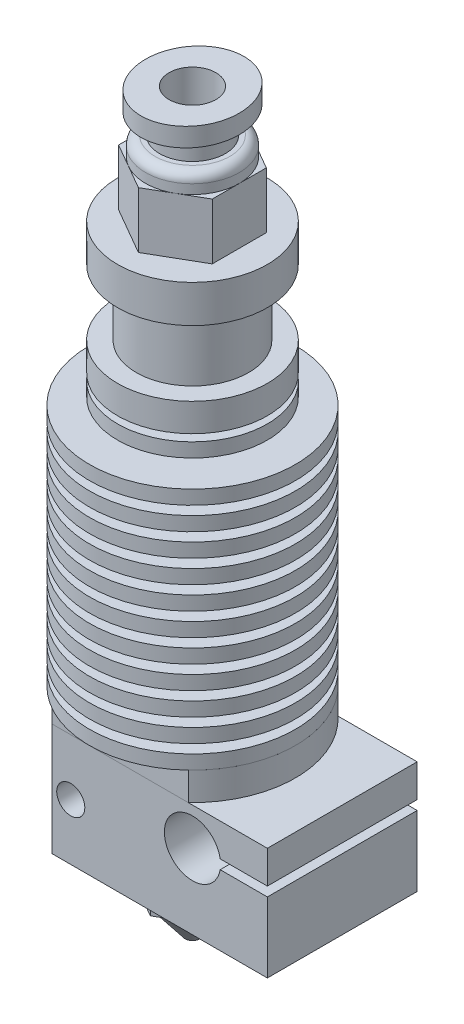
SolidWorks part; units mm, degrees
material "Bronce de aluminio"
ref_plane "Alzado" through (0, 0, 0) normal (0, 0, 1) x (1, 0, 0)
ref_plane "Planta" through (0, 0, 0) normal (0, 1, 0) x (1, 0, 0)
ref_plane "Vista lateral" through (0, 0, 0) normal (1, 0, 0) x (0, 0, -1)
sketch "Croquis1" plane through (0, 0, 0) normal (0, 0, 1) x (1, 0, 0)
  line L0 (0, 0) -> (-8, 0)
  line L1 (-8, 0) -> (-8, -4)
  line L2 (-8, -4) -> (-6, -4)
  line L3 (-6, -4) -> (-6, -11)
  line L4 (-6, -11) -> (-8, -11)
  line L5 (-8, -11) -> (-8, -14)
  line L6 (-8, -14) -> (-5, -14)
  line L7 (-5, -14) -> (-5, -14.75)
  line L8 (-5, -14.75) -> (-8, -14.75)
  line L9 (-8, -14.75) -> (-8, -16.25)
  line L10 (-8, -16.25) -> (-5, -16.25)
  line L12 (-5, -17) -> (-11, -17)
  line L13 (-11, -17) -> (-11, -18.5)
  line L17 (-5, -16.25) -> (-5, -17)
  line L18 (-11, -18.5) -> (-5, -18.5)
  line L19 (-5, -18.5) -> (-5, -19.45)
  line L20 (-5, -19.45) -> (-11, -19.45)
  line L21 (-11, -19.45) -> (-11, -20.95)
  line L22 (-11, -20.95) -> (-5, -20.95)
  line L23 (-5, -20.95) -> (-5, -21.9)
  line L24 (-5, -21.9) -> (-11, -21.9)
  line L25 (-11, -21.9) -> (-11, -23.4)
  line L26 (-11, -23.4) -> (-5, -23.4)
  line L27 (-5, -23.4) -> (-5, -24.35)
  line L28 (-5, -24.35) -> (-11, -24.35)
  line L29 (-11, -24.35) -> (-11, -25.85)
  line L30 (-11, -25.85) -> (-5, -25.85)
  line L31 (-5, -25.85) -> (-5, -26.8)
  line L32 (-5, -26.8) -> (-11, -26.8)
  line L33 (-11, -26.8) -> (-11, -28.3)
  line L34 (-11, -28.3) -> (-5, -28.3)
  line L35 (-5, -28.3) -> (-5, -29.25)
  line L36 (-5, -29.25) -> (-11, -29.25)
  line L37 (-11, -29.25) -> (-11, -30.75)
  line L38 (-11, -30.75) -> (-5, -30.75)
  line L39 (-5, -30.75) -> (-5, -31.7)
  line L40 (-5, -31.7) -> (-11, -31.7)
  line L41 (-11, -31.7) -> (-11, -33.2)
  line L42 (-11, -33.2) -> (-5, -33.2)
  line L43 (-5, -33.2) -> (-5, -34.15)
  line L44 (-5, -34.15) -> (-11, -34.15)
  line L45 (-11, -34.15) -> (-11, -35.65)
  line L46 (-11, -35.65) -> (-5, -35.65)
  line L47 (-5, -35.65) -> (-5, -36.6)
  line L48 (-5, -36.6) -> (-11, -36.6)
  line L49 (-11, -36.6) -> (-11, -38.1)
  line L50 (-11, -38.1) -> (-5, -38.1)
  line L51 (-5, -38.1) -> (-5, -39.05)
  line L52 (-5, -39.05) -> (-11, -39.05)
  line L53 (-11, -39.05) -> (-11, -40.55)
  line L55 (0, 0) -> (0, -43)
  line L56 (-11, -40.55) -> (-5, -40.55)
  line L57 (-5, -40.55) -> (-5, -41.5)
  line L58 (-5, -41.5) -> (-11, -41.5)
  line L59 (-11, -41.5) -> (-11, -43)
  line L60 (-11, -43) -> (0, -43)
  point P18 (-8, -15.5)
  dimension "D1" = 8
  dimension "D2" = 4
  dimension "D3" = 0.95
  dimension "D4" = 6
  dimension "D5" = 3
  dimension "D6" = 1.5
  dimension "D7" = 1.5
  dimension "D8" = 17
  dimension "D9" = 6
  dimension "D10" = 11
  dimension "D11" = 1.5
  dimension "D12" = 5
  dimension "D13" = 1.5
  dimension "D14" = 1.5
  dimension "D15" = 0.95
  dimension "D16" = 0.95
  dimension "D17" = 1.5
  dimension "D18" = 0.95
  dimension "D19" = 1.5
  dimension "D20" = 0.95
  dimension "D21" = 1.5
  dimension "D22" = 0.95
  dimension "D23" = 1.5
  dimension "D24" = 0.95
  dimension "D25" = 1.5
  dimension "D26" = 0.95
  dimension "D27" = 1.5
  dimension "D28" = 0.95
  dimension "D29" = 1.5
  dimension "D30" = 1.5
  dimension "D31" = 0.95
revolve "Revolución1" add sketch "Croquis1" angle 360 about L55
sketch "Croquis3" plane through (0, -43, 0) normal (0, -1, 0) x (1, 0, 0)
  circle A0 centre (0, 0) radius 6
  dimension "D1" = 12
extrude "Saliente-Extruir1" add sketch "Croquis3" against normal blind 28 draft 2
sketch "Croquis4" plane through (0, 0, 0) normal (0, 1, 0) x (1, 0, 0)
  circle A0 centre (0, 0) radius 4.5
  dimension "D1" = 9
extrude "Cortar-Extruir1" cut sketch "Croquis4" against normal blind 11
sketch "Croquis5" plane through (0, -11, 0) normal (0, 1, 0) x (1, 0, 0)
  circle A0 centre (0, 0) radius 2.5
  dimension "D1" = 5
extrude "Cortar-Extruir2" cut sketch "Croquis5" against normal through all
sketch "Croquis6" plane through (0, -43, 0) normal (0, -1, 0) x (1, 0, 0)
  circle A0 centre (0, 0) radius 3.5
  dimension "D1" = 7
extrude "Cortar-Extruir3" cut sketch "Croquis6" against normal up to surface (29 mm away) up to face at (-5, -14, 0)
sketch "Croquis13" plane through (0, -43, 0) normal (0, -1, 0) x (1, 0, 0)
  line L1 (-7, 8) -> (7.5498, 8)
  line L2 (-7, 8) -> (-7, -8)
  line L3 (-7, -8) -> (7.5498, -8)
  circle A0 centre (0, 0) radius 4
  circle A1 centre (0, 0) radius 11 construction
  arc A2 (7.5498, -8) -> (7.5498, 8) centre (0, 0) ccw
  dimension "D1" = 8
  dimension "D3" = 16
  dimension "D4" = 8
  dimension "D5" = 7
extrude "Saliente-Extruir6" add sketch "Croquis13" along normal blind 3 separate body
sketch "Croquis7" plane through (0, 0, 0) normal (0, 0, 1) x (1, 0, 0)
  line L1 (-7, -46) -> (16, -46)
  line L2 (-7, -46) -> (-7, -58)
  line L3 (-7, -58) -> (16, -58)
  line L4 (16, -46) -> (16, -58)
  line L5 (7.5498, -46) -> (-7, -46) construction
  dimension "D1" = 12
  dimension "D2" = 23
  dimension "D3" = 7
extrude "Saliente-Extruir2" add sketch "Croquis7" along normal mid plane 16 separate body
sketch "Croquis8" plane through (0, 0, 8) normal (0, 0, 1) x (1, 0, 0)
  line L0 (-7, -58) -> (16, -58) construction
  line L1 (16, -58) -> (16, -46) construction
  line L2 (-7, -46) -> (-7, -58) construction
  line L4 (10.958, -49.5) -> (16, -49.5)
  line L6 (10.958, -50.5) -> (16, -50.5)
  line L7 (16, -49.5) -> (16, -50.5)
  arc A0 (10.958, -49.5) -> (10.958, -50.5) centre (8, -50) ccw
  circle A1 centre (-5, -52) radius 1.5
  dimension "D1" = 3
  dimension "D2" = 6
  dimension "D3" = 8
  dimension "D4" = 8
  dimension "D5" = 2
  dimension "D6" = 6
  dimension "D7" = 1
  dimension "D8" = 5.042
extrude "Cortar-Extruir4" cut sketch "Croquis8" against normal through all
sketch "Croquis9" plane through (0, -46, 0) normal (0, 1, 0) x (1, 0, 0)
  circle A0 centre (0, 0) radius 3
  dimension "D1" = 6
extrude "Cortar-Extruir5" cut sketch "Croquis9" against normal through all
sketch "Croquis10" plane through (0, -58, 0) normal (0, -1, 0) x (1, 0, 0)
  line L1 (0, 4.5) -> (-3.8971, 2.25)
  line L2 (-3.8971, 2.25) -> (-3.8971, -2.25)
  line L3 (-3.8971, -2.25) -> (0, -4.5)
  line L4 (0, -4.5) -> (3.8971, -2.25)
  line L5 (3.8971, -2.25) -> (3.8971, 2.25)
  line L6 (3.8971, 2.25) -> (0, 4.5)
  circle A0 centre (0, 0) radius 3.8971 construction
  dimension "D1" = 9
extrude "Saliente-Extruir3" add sketch "Croquis10" along normal blind 4 separate body
sketch "Croquis11" plane through (0, -62, 0) normal (0, -1, 0) x (1, 0, 0)
  line L0 (3.8971, 2.25) -> (0, 4.5) construction
  circle A0 centre (0, 0) radius 3.8971
extrude "Saliente-Extruir4" add sketch "Croquis11" along normal blind 4 draft 38
sketch "Croquis12" plane through (0, 0, 0) normal (0, 1, 0) x (1, 0, 0)
  line L1 (0, 5.775) -> (-5.0013, 2.8875)
  line L2 (-5.0013, 2.8875) -> (-5.0013, -2.8875)
  line L3 (-5.0013, -2.8875) -> (0, -5.775)
  line L4 (0, -5.775) -> (5.0013, -2.8875)
  line L5 (5.0013, -2.8875) -> (5.0013, 2.8875)
  line L6 (5.0013, 2.8875) -> (0, 5.775)
  circle A0 centre (0, 0) radius 5.0013 construction
  dimension "D1" = 11.55
extrude "Saliente-Extruir5" add sketch "Croquis12" along normal blind 6 separate body
sketch "Croquis14" plane through (0, 6, 0) normal (0, 1, 0) x (1, 0, 0)
  circle A0 centre (0, 0) radius 5.0013
extrude "Saliente-Extruir7" add sketch "Croquis14" along normal blind 2
fillet "Redondeo4" radius 1 1 edges at (-5.0013, 8, 0)
sketch "Croquis15" plane through (0, 8, 0) normal (0, 1, 0) x (1, 0, 0)
  circle A0 centre (0, 0) radius 3.5013
  circle A1 centre (0, 0) radius 4.0013 construction
  dimension "D1" = 0.5
extrude "Saliente-Extruir8" add sketch "Croquis15" along normal blind 1.5
sketch "Croquis16" plane through (0, 9.5, 0) normal (0, 1, 0) x (1, 0, 0)
  circle A0 centre (0, 0) radius 2.6342
extrude "Saliente-Extruir9" add sketch "Croquis16" along normal blind 1
sketch "Croquis17" plane through (0, 10.5, 0) normal (0, 1, 0) x (1, 0, 0)
  ellipse E0 centre (0, 0) end of major axis (0, -5.5) minor radius 5
  dimension "D1" = 10
  dimension "D2" = 11
extrude "Saliente-Extruir10" add sketch "Croquis17" along normal blind 2
sketch "Croquis18" plane through (0, 12.5, 0) normal (0, 1, 0) x (1, 0, 0)
  circle A0 centre (0, 0) radius 2.5
  dimension "D1" = 5
extrude "Cortar-Extruir6" cut sketch "Croquis18" against normal blind 14
sketch "Croquis19" plane through (0, -66, 0) normal (0, -1, 0) x (1, 0, 0)
  circle A0 centre (0, 0) radius 0.75
  dimension "D1" = 1.5
extrude "Cortar-Extruir7" cut sketch "Croquis19" against normal blind 10
ref_axis "Eje1" through (0, 47.4375, 0) along (0, -1, 0)
